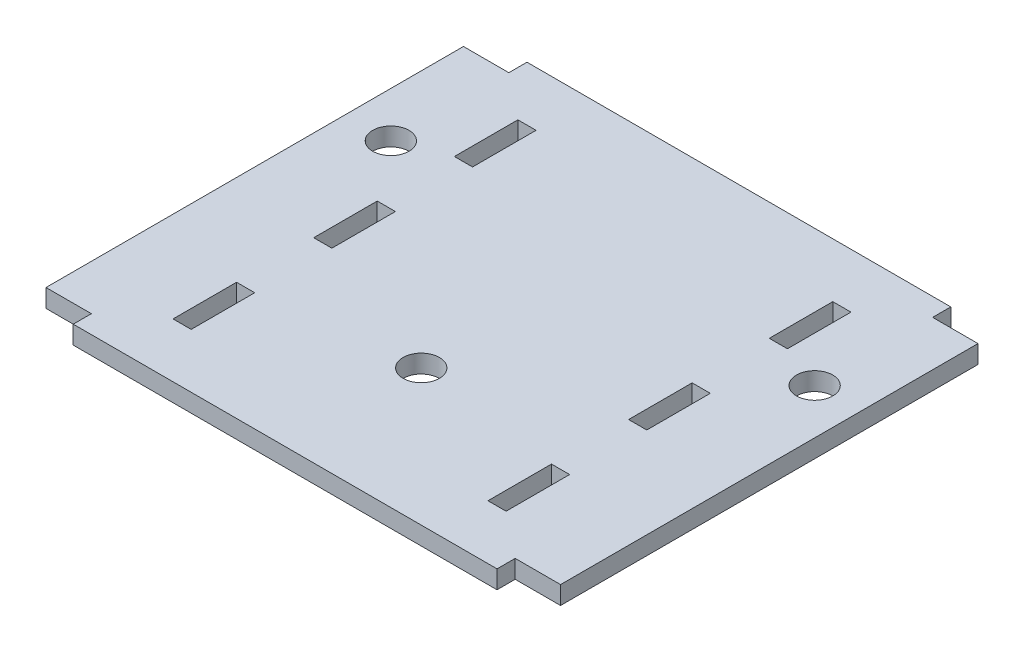
SolidWorks part; units mm, degrees
ref_plane "Front Plane" through (0, 0, 0) normal (0, 0, 1) x (1, 0, 0)
ref_plane "Top Plane" through (0, 0, 0) normal (0, 1, 0) x (1, 0, 0)
ref_plane "Right Plane" through (0, 0, 0) normal (1, 0, 0) x (0, 0, -1)
sketch "Sketch1" plane through (0, 0, 0) normal (0, 1, 0) x (1, 0, 0)
  line L0 (-35.6495, -41.9807) -> (-37.6495, -41.9807)
  line L1 (-70.7995, 2.0193) -> (32.2005, 2.0193)
  line L2 (-70.7995, 2.0193) -> (-70.7995, -47.9807)
  line L3 (-70.7995, -47.9807) -> (32.2005, -47.9807)
  line L4 (32.2005, 2.0193) -> (32.2005, -47.9807)
  line L5 (-35.6495, -41.9807) -> (-35.6495, -34.9807)
  line L6 (-35.6495, -34.9807) -> (-37.6495, -34.9807)
  line L7 (-37.6495, -41.9807) -> (-37.6495, -34.9807)
  line L8 (-35.6495, -26.4807) -> (-37.6495, -26.4807)
  line L9 (-35.6495, -26.4807) -> (-35.6495, -19.4807)
  line L10 (-35.6495, -19.4807) -> (-37.6495, -19.4807)
  line L11 (-37.6495, -26.4807) -> (-37.6495, -19.4807)
  line L12 (-35.6495, -10.9807) -> (-37.6495, -10.9807)
  line L13 (-35.6495, -10.9807) -> (-35.6495, -3.9807)
  line L14 (-35.6495, -3.9807) -> (-37.6495, -3.9807)
  line L15 (-37.6495, -10.9807) -> (-37.6495, -3.9807)
  line L16 (-0.9495, -10.9807) -> (-2.9495, -10.9807)
  line L17 (-0.9495, -10.9807) -> (-0.9495, -3.9807)
  line L18 (-0.9495, -3.9807) -> (-2.9495, -3.9807)
  line L19 (-2.9495, -10.9807) -> (-2.9495, -3.9807)
  line L20 (-0.9495, -26.4807) -> (-2.9495, -26.4807)
  line L21 (-0.9495, -26.4807) -> (-0.9495, -19.4807)
  line L22 (-0.9495, -19.4807) -> (-2.9495, -19.4807)
  line L23 (-2.9495, -26.4807) -> (-2.9495, -19.4807)
  line L24 (-0.9495, -41.9807) -> (-2.9495, -41.9807)
  line L25 (-0.9495, -41.9807) -> (-0.9495, -34.9807)
  line L26 (-0.9495, -34.9807) -> (-2.9495, -34.9807)
  line L27 (-2.9495, -41.9807) -> (-2.9495, -34.9807)
  line L29 (-47.6495, -47.9807) -> (-42.6495, -47.9807)
  line L30 (-47.6495, -47.9807) -> (-47.6495, -45.9807)
  line L31 (-47.6495, -45.9807) -> (-42.6495, -45.9807)
  line L32 (-42.6495, -47.9807) -> (-42.6495, -45.9807)
  line L33 (4.0505, -47.9807) -> (9.0505, -47.9807)
  line L34 (4.0505, -47.9807) -> (4.0505, -45.9807)
  line L35 (4.0505, -45.9807) -> (9.0505, -45.9807)
  line L36 (9.0505, -47.9807) -> (9.0505, -45.9807)
  line L37 (-47.6495, 2.0193) -> (-42.6495, 2.0193)
  line L38 (-47.6495, 2.0193) -> (-47.6495, 0.0193)
  line L39 (-47.6495, 0.0193) -> (-42.6495, 0.0193)
  line L40 (-42.6495, 2.0193) -> (-42.6495, 0.0193)
  line L41 (4.0505, 2.0193) -> (9.0505, 2.0193)
  line L42 (4.0505, 2.0193) -> (4.0505, 0.0193)
  line L43 (4.0505, 0.0193) -> (9.0505, 0.0193)
  line L44 (9.0505, 2.0193) -> (9.0505, 0.0193)
  circle A0 centre (-42.6495, -12.9807) radius 2
  circle A1 centre (4.0505, -12.9807) radius 2
  circle A2 centre (-19.2995, -32.9807) radius 2
  dimension "D21" = 4
  dimension "D22" = 4
  dimension "D24" = 32.7
  dimension "D25" = 32.7
  dimension "D27" = 15
  dimension "D29" = 4
  dimension "D31" = 51.5
  dimension "D1" = 50
  dimension "D2" = 103
  dimension "D4" = 7
  dimension "D5" = 2
  dimension "D6" = 7
  dimension "D7" = 2
  dimension "D8" = 7
  dimension "D9" = 2
  dimension "D10" = 7
  dimension "D11" = 2
  dimension "D12" = 7
  dimension "D13" = 2
  dimension "D14" = 7
  dimension "D15" = 2
  dimension "D16" = 8.5
  dimension "D17" = 8.5
  dimension "D18" = 8.5
  dimension "D19" = 8.5
  dimension "D20" = 32.7
  dimension "D23" = 0
  dimension "D26" = 0
  dimension "D28" = 15
  dimension "D30" = 35
  dimension "D32" = 0
  dimension "D33" = 0
  dimension "D34" = 0
  dimension "D35" = 6
  dimension "D36" = 6
  dimension "D37" = 6
  dimension "D38" = 6
  dimension "D39" = 33.15
  dimension "D40" = 33.15
  dimension "D41" = 16.35
  dimension "D42" = 16.35
  dimension "D43" = 2
  dimension "D44" = 5
  dimension "D45" = 5
  dimension "D46" = 2
  dimension "D47" = 5
  dimension "D48" = 5
  dimension "D49" = 5
  dimension "D50" = 5
  dimension "D51" = 2
  dimension "D52" = 5
  dimension "D53" = 5
  dimension "D54" = 2
  dimension "D55" = 35
extrude "Boss-Extrude1" add sketch "Sketch1" along normal blind 2 contours L1 L44 L43 L42 L40 L39 L38 L2 L3 L30 L31 L32 L34 L35 L36 L4 A2 A1 A0 L0 L7 L6 L5 L8 L11 L10 L9 L12 L15 L14 L13 L16 L19 L18 L17 L20 L23 L22 L21 region at (-19.2995, 0, 23.0059)
sketch "Sketch2" plane through (0, 0, 0) normal (0, -1, 0) x (-1, 0, 0)
  line L1 (70.7995, -47.9807) -> (47.6495, -47.9807)
  line L2 (70.7995, -47.9807) -> (70.7995, 2.0193)
  line L3 (70.7995, 2.0193) -> (47.6495, 2.0193)
  line L4 (47.6495, -47.9807) -> (47.6495, 2.0193)
  line L5 (-32.2005, -47.9807) -> (-9.0505, -47.9807)
  line L6 (-32.2005, -47.9807) -> (-32.2005, 2.0193)
  line L7 (-32.2005, 2.0193) -> (-9.0505, 2.0193)
  line L8 (-9.0505, -47.9807) -> (-9.0505, 2.0193)
extrude "Cut-Extrude1" cut sketch "Sketch2" against normal blind 10
